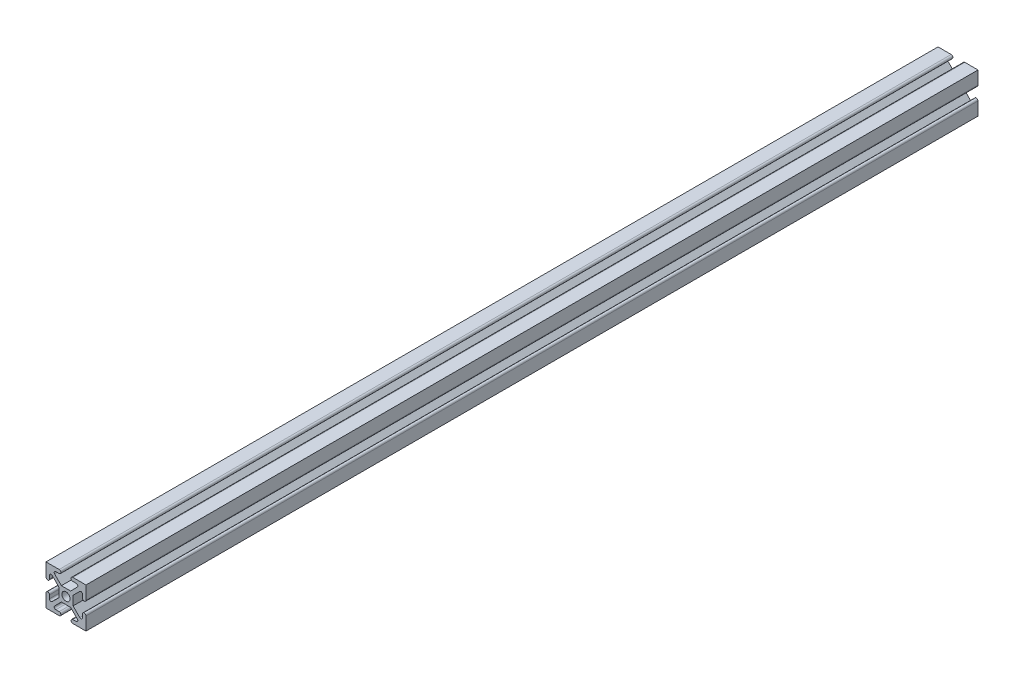
SolidWorks part; units mm, degrees
ref_plane "Front Plane" through (0, 0, 0) normal (0, 0, 1) x (1, 0, 0)
ref_plane "Top Plane" through (0, 0, 0) normal (0, 1, 0) x (1, 0, 0)
ref_plane "Right Plane" through (0, 0, 0) normal (1, 0, 0) x (0, 0, -1)
sketch "Sketch1" plane through (0, 0, 0) normal (0, 0, 1) x (1, 0, 0)
  line L3 (-4.3434, -10.4903) -> (-6.4748, -10.4903)
  line L7 (6.4748, -10.4903) -> (4.3434, -10.4903)
  line L12 (10.4903, -4.3434) -> (10.4903, -6.475)
  line L16 (10.4903, 6.4748) -> (10.4903, 4.3434)
  line L21 (4.3434, 10.4901) -> (6.4747, 10.4901)
  line L25 (-6.4748, 10.4901) -> (-4.3434, 10.4901)
  line L30 (-10.4903, 4.3434) -> (-10.4903, 6.4748)
  line L34 (-10.4903, -6.4748) -> (-10.4903, -4.3434)
  line L42 (-12.7001, 4.3434) -> (-12.7001, 12.6999)
  line L43 (-12.7001, 12.6999) -> (-4.3434, 12.6999)
  line L44 (4.3434, 12.6999) -> (12.7001, 12.6999)
  line L45 (12.7001, 12.6999) -> (12.7001, 4.3434)
  line L46 (4.3434, -12.7001) -> (12.6999, -12.7001)
  line L47 (12.6999, -12.7001) -> (12.6999, -4.3434)
  line L48 (-4.3434, -12.7001) -> (-12.7001, -12.7001)
  line L49 (-12.7001, -12.7001) -> (-12.7001, -4.3434)
  line L50 (-7.1933, -8.7558) -> (-2.9333, -4.4958)
  line L51 (-8.7558, -7.1933) -> (-4.4958, -2.9333)
  line L52 (-8.7558, 7.1933) -> (-4.4958, 2.9333)
  line L53 (-4.4958, -2.9333) -> (-4.4958, 2.9333)
  line L54 (2.9333, -4.4958) -> (-2.9333, -4.4958)
  line L55 (2.9333, -4.4958) -> (7.1933, -8.7558)
  line L56 (8.7558, -7.1934) -> (4.4958, -2.9334)
  line L57 (4.4958, 2.9333) -> (4.4958, -2.9334)
  line L58 (4.4958, 2.9333) -> (8.7558, 7.1933)
  line L59 (7.1932, 8.7557) -> (2.9331, 4.4957)
  line L60 (-2.9333, 4.4957) -> (2.9331, 4.4957)
  line L61 (-2.9333, 4.4957) -> (-7.1933, 8.7557)
  circle A0 centre (0, 0) radius 2.6035
  arc A6 (-4.3434, -12.7001) -> (-4.3434, -10.4903) centre (-4.3434, -11.5952) ccw
  arc A7 (-6.4748, -10.4903) -> (-7.1933, -8.7558) centre (-6.4748, -9.4743) cw
  arc A10 (7.1933, -8.7558) -> (6.4748, -10.4903) centre (6.4748, -9.4743) cw
  arc A11 (4.3434, -10.4903) -> (4.3434, -12.7001) centre (4.3434, -11.5952) ccw
  arc A17 (12.6999, -4.3434) -> (10.4903, -4.3434) centre (11.5951, -4.3434) ccw
  arc A18 (10.4903, -6.475) -> (8.7558, -7.1934) centre (9.4743, -6.475) cw
  arc A21 (8.7558, 7.1933) -> (10.4903, 6.4748) centre (9.4743, 6.4748) cw
  arc A22 (10.4903, 4.3434) -> (12.7001, 4.3434) centre (11.5952, 4.3434) ccw
  arc A28 (4.3434, 12.6999) -> (4.3434, 10.4901) centre (4.3434, 11.595) ccw
  arc A29 (6.4747, 10.4901) -> (7.1932, 8.7557) centre (6.4747, 9.4741) cw
  arc A32 (-7.1933, 8.7557) -> (-6.4748, 10.4901) centre (-6.4748, 9.4741) cw
  arc A33 (-4.3434, 10.4901) -> (-4.3434, 12.6999) centre (-4.3434, 11.595) ccw
  arc A39 (-12.7001, 4.3434) -> (-10.4903, 4.3434) centre (-11.5952, 4.3434) ccw
  arc A40 (-10.4903, 6.4748) -> (-8.7558, 7.1933) centre (-9.4743, 6.4748) cw
  arc A43 (-8.7558, -7.1933) -> (-10.4903, -6.4748) centre (-9.4743, -6.4748) cw
  arc A44 (-10.4903, -4.3434) -> (-12.7001, -4.3434) centre (-11.5952, -4.3434) ccw
  point P2 (-0.0001, 4.4957)
  point P6 (-4.4958, 0)
  point P7 (4.4958, -0.0001)
  point P8 (0, -4.4958)
  point P21 (-4.4958, 0)
  point P23 (0, -4.4958)
  point P26 (4.4958, -0.0001)
  point P35 (-0.0001, 4.4957)
  dimension "D1" = 25.4
  dimension "D2" = 25.4
extrude "Boss-Extrude1" add sketch "Sketch1" against normal blind 566.7375
